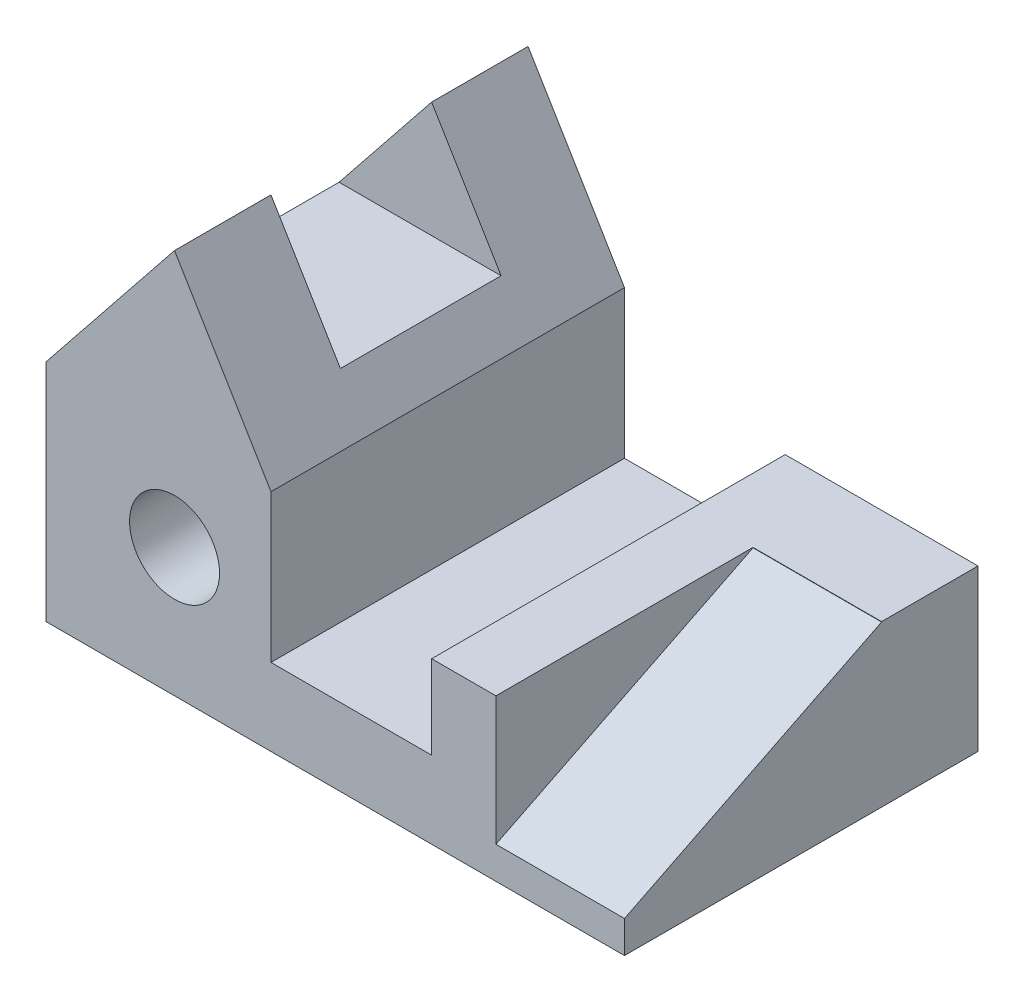
SolidWorks part; units mm, degrees
ref_plane "Front Plane" through (0, 0, 0) normal (0, 0, 1) x (1, 0, 0)
ref_plane "Top Plane" through (0, 0, 0) normal (0, 1, 0) x (1, 0, 0)
ref_plane "Right Plane" through (0, 0, 0) normal (1, 0, 0) x (0, 0, -1)
sketch "Sketch1" plane through (0, 0, 0) normal (0, 1, 0) x (1, 0, 0)
  line L1 (0, 0) -> (90, 0)
  line L2 (0, 0) -> (0, -55)
  line L3 (0, -55) -> (90, -55)
  line L4 (90, 0) -> (90, -55)
  dimension "D1" = 90
  dimension "D2" = 55
extrude "Boss-Extrude1" add sketch "Sketch1" along normal blind 5
sketch "Sketch2" plane through (0, 5, 0) normal (0, 1, 0) x (1, 0, 0)
  line L0 (0, -55) -> (90, -55) construction
  line L1 (0, 0) -> (35, 0)
  line L2 (0, 0) -> (0, -55)
  line L3 (0, -55) -> (35, -55)
  line L4 (35, 0) -> (35, -55)
  line L7 (90, 0) -> (60, 0)
  line L8 (90, 0) -> (90, -55)
  line L9 (90, -55) -> (60, -55)
  line L10 (60, 0) -> (60, -55)
  dimension "D1" = 35
  dimension "D2" = 30
extrude "Boss-Extrude2" add sketch "Sketch2" along normal blind 30 contours L1 L4 L3 L2
sketch "Sketch5" plane through (0, 5, 0) normal (0, 1, 0) x (1, 0, 0)
  line L0 (35, -55) -> (90, -55) construction
  line L6 (60, 0) -> (70, 0)
  line L7 (60, 0) -> (60, -55)
  line L8 (60, -55) -> (70, -55)
  line L9 (70, 0) -> (70, -55)
  dimension "D1" = 55
  dimension "D2" = 10
hole_wizard "Ø1.0mm Dowel Hole1" positions "Sketch6" profile "Sketch7" hole size "Ø1.0" standard "ANSI Metric" end condition through all
sketch "Sketch6" plane through (0, 0, 55) normal (0, 0, 1) x (1, 0, 0)
  line L0 (0, 35) -> (0, 0) construction
  line L1 (0, 0) -> (90, 0) construction
  point P0 (20, 20)
  dimension "D1" = 20
  dimension "D2" = 20
sketch "Sketch7" plane through (20, 20, 55) normal (1, 0, 0) x (0, -1, 0)
  line L0 (0, 0) -> (0, 55)
  line L1 (0, 55) -> (7, 55)
  line L2 (7, 55) -> (7, 0)
  line L5 (7, 0) -> (0, 0)
  line L11 (0, -6.35) -> (0, 107.95) construction
  dimension "Thru Hole Dia." = 14
  dimension "Thru Hole Depth" = 55
extrude "Boss-Extrude4" add sketch "Sketch5" along normal blind 20
sketch "Sketch8" plane through (0, 5, 0) normal (0, 1, 0) x (1, 0, 0)
  line L0 (90, -55) -> (90, 0) construction
  line L1 (70, 0) -> (90, 0)
  line L2 (70, 0) -> (70, -15)
  line L3 (70, -15) -> (90, -15)
  line L4 (90, 0) -> (90, -15)
  dimension "D1" = 15
extrude "Boss-Extrude5" add sketch "Sketch8" along normal blind 20
chamfer "Chamfer1" distance 40 angle 26.5 1 edges at (80, 5, 15) first distance on face at (80, 5, 35)
sketch "Sketch9" plane through (0, 5, 0) normal (0, 1, 0) x (1, 0, 0)
  line L1 (35, 0) -> (60, 0)
  line L2 (35, 0) -> (35, -55)
  line L3 (35, -55) -> (60, -55)
  line L4 (60, 0) -> (60, -55)
extrude "Boss-Extrude6" add sketch "Sketch9" along normal blind 7
sketch "Sketch12" plane through (0, 0, 55) normal (0, 0, 1) x (1, 0, 0)
  line L0 (0, 35) -> (20, 60)
  line L1 (20, 60) -> (35, 35)
  line L2 (20, 60) -> (20, 20) construction
  line L13 (0, 0) -> (90, 0)
  line L14 (90, 0) -> (90, 5)
  line L15 (90, 5) -> (70, 5)
  line L16 (70, 5) -> (70, 25)
  line L17 (70, 25) -> (60, 25)
  line L18 (60, 25) -> (60, 12)
  line L19 (60, 12) -> (35, 12)
  line L20 (35, 12) -> (35, 35)
  line L21 (35, 35) -> (0, 35)
  line L22 (0, 35) -> (0, 0)
  line L23 (0, 0) -> (90, 0)
  line L24 (90, 0) -> (90, 5)
  line L25 (90, 5) -> (70, 5)
  line L26 (70, 5) -> (70, 25)
  line L27 (70, 25) -> (60, 25)
  line L28 (60, 25) -> (60, 12)
  line L29 (60, 12) -> (35, 12)
  line L30 (35, 12) -> (35, 35)
  line L32 (0, 35) -> (0, 0)
  circle A0 centre (20, 20) radius 7 construction
  dimension "D3" = 0
  dimension "D1" = 40
  dimension "D2" = 40
extrude "Boss-Extrude7" add sketch "Sketch12" against normal blind 55
sketch "Sketch16" plane through (0, 0, 0) normal (-1, 0, 0) x (0, 0, 1)
  line L0 (0, 60) -> (55, 60) construction
  line L1 (15, 60) -> (40, 60)
  line L2 (15, 60) -> (15, 42)
  line L3 (15, 42) -> (40, 42)
  line L4 (40, 60) -> (40, 42)
  line L5 (0, 60) -> (0, 35) construction
  line L6 (55, 60) -> (55, 35) construction
  dimension "D1" = 15
  dimension "D2" = 15
  dimension "D3" = 18
extrude "Boss-Extrude8" add sketch "Sketch16" against normal blind 43
sketch "Sketch17" plane through (0, 0, 0) normal (-1, 0, 0) x (0, 0, 1)
  line L1 (15, 60) -> (40, 60)
  line L2 (15, 60) -> (15, 42)
  line L3 (15, 42) -> (40, 42)
  line L4 (40, 60) -> (40, 42)
extrude "Cut-Extrude1" cut sketch "Sketch17" against normal blind 43
hole_wizard "Ø1.0mm Dowel Hole2" positions "Sketch13" profile "Sketch15" hole size "Ø1.0" standard "ANSI Metric" end condition through all
sketch "Sketch13" plane through (0, 0, 55) normal (0, 0, 1) x (1, 0, 0)
  line L0 (0, 35) -> (0, 0) construction
  line L1 (0, 0) -> (90, 0) construction
  point P0 (20, 20)
  dimension "D1" = 20
  dimension "D2" = 20
sketch "Sketch15" plane through (20, 20, 55) normal (1, 0, 0) x (0, -1, 0)
  line L0 (0, 0) -> (0, 55)
  line L1 (0, 55) -> (7, 55)
  line L2 (7, 55) -> (7, 0)
  line L5 (7, 0) -> (0, 0)
  line L11 (0, -6.35) -> (0, 107.95) construction
  dimension "Thru Hole Dia." = 14
  dimension "Thru Hole Depth" = 55
